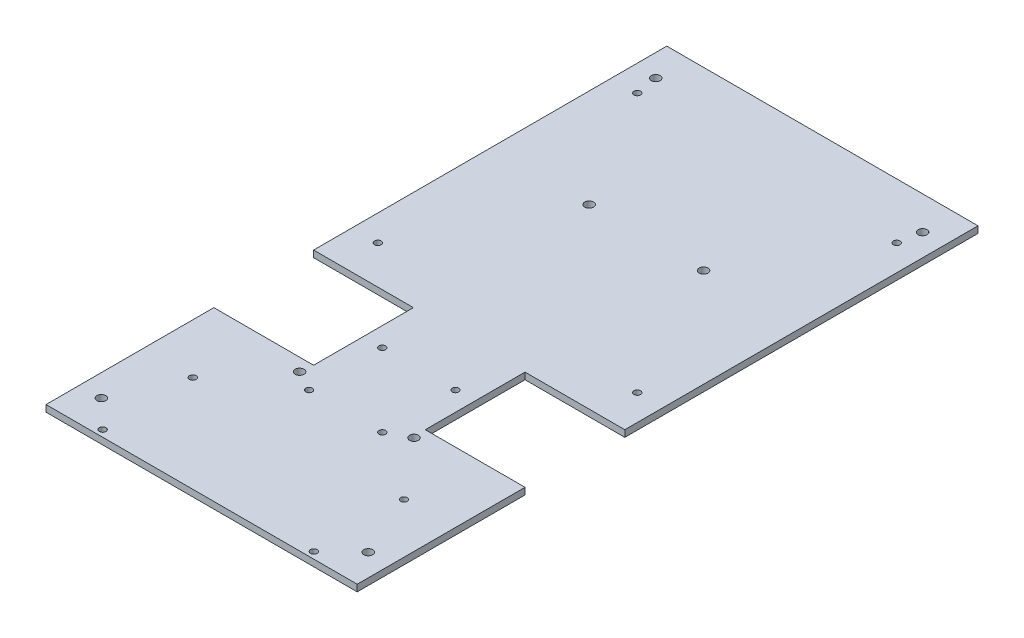
SolidWorks part; units mm, degrees
material "PMMA"
ref_plane "Front Plane" through (0, 0, 0) normal (0, 0, 1) x (1, 0, 0)
ref_plane "Top Plane" through (0, 0, 0) normal (0, 1, 0) x (1, 0, 0)
ref_plane "Right Plane" through (0, 0, 0) normal (1, 0, 0) x (0, 0, -1)
sketch "Schizzo1" plane through (0, 0, 0) normal (0, 1, 0) x (1, 0, 0)
  line L0 (-26.6704, 112.0472) -> (-26.6704, -167.9528) construction
  line L1 (-96.8504, 112.0472) -> (43.5096, 112.0472)
  line L2 (-96.8504, 112.0472) -> (-96.8504, -167.9528)
  line L3 (-96.8504, -167.9528) -> (43.5096, -167.9528)
  line L4 (43.5096, 112.0472) -> (43.5096, -167.9528)
  line L5 (-96.8504, -127.9528) -> (43.5096, -127.9528) construction
  line L6 (-96.8504, 12.0472) -> (43.5096, 12.0472) construction
  dimension "D1" = 280
  dimension "D2" = 140.36
  dimension "D3" = 40
  dimension "D4" = 100
extrude "Estrusione-Estrusione1" add sketch "Schizzo1" along normal blind 3
sketch "Schizzo2" plane through (0, 3, 0) normal (0, 1, 0) x (1, 0, 0)
  line L0 (-96.8504, 112.0472) -> (-96.8504, -167.9528) construction
  line L1 (-96.8504, -167.9528) -> (43.5096, -167.9528) construction
  line L2 (-26.6704, -167.9528) -> (-26.6704, 112.0472) construction
  line L3 (43.5096, 112.0472) -> (-96.8504, 112.0472) construction
  line L4 (-96.8504, -27.9528) -> (43.5096, -27.9528) construction
  line L5 (43.5096, -167.9528) -> (43.5096, 112.0472) construction
  circle A0 centre (-86.8504, -152.9528) radius 2
  circle A1 centre (33.5096, -152.9528) radius 2
  circle A2 centre (-86.8504, 97.0472) radius 2
  circle A3 centre (33.5096, 97.0472) radius 2
  point P16 (33.5096, 97.0472)
  dimension "D1" = 4
  dimension "D2" = 10
  dimension "D3" = 15
  dimension "D4" = 120.36
extrude "Taglio-Estrusione1" cut sketch "Schizzo2" along direction (0, 1, 0) on the side against the normal through all
sketch "Schizzo3" plane through (0, 0, 0) normal (0, 1, 0) x (1, 0, 0)
  line L0 (-96.8504, -92.2528) -> (43.5096, -92.2528) construction
  line L1 (-96.8504, 112.0472) -> (-96.8504, -167.9528) construction
  line L2 (43.5096, -167.9528) -> (43.5096, 112.0472) construction
  line L3 (-96.8504, -167.9528) -> (43.5096, -167.9528) construction
  line L4 (-26.6704, 112.0472) -> (-26.6704, -167.9528) construction
  line L5 (-96.8504, -92.2528) -> (-51.8504, -92.2528)
  line L6 (-96.8504, -92.2528) -> (-96.8504, -47.2528)
  line L7 (-96.8504, -47.2528) -> (-51.8504, -47.2528)
  line L8 (-51.8504, -92.2528) -> (-51.8504, -47.2528)
  line L9 (43.5096, 112.0472) -> (-96.8504, 112.0472) construction
  line L10 (43.5096, -92.2528) -> (43.5096, -47.2528)
  line L11 (43.5096, -92.2528) -> (-1.4904, -92.2528)
  line L12 (-1.4904, -92.2528) -> (-1.4904, -47.2528)
  line L13 (43.5096, -47.2528) -> (-1.4904, -47.2528)
  dimension "D1" = 75.7
  dimension "D2" = 45
  dimension "D3" = 45
extrude "Taglio-Estrusione2" cut sketch "Schizzo3" along direction (0, 1, 0) on the side of the normal through all
sketch "Schizzo4" plane through (0, 0, 0) normal (0, 1, 0) x (1, 0, 0)
  line L0 (-26.6704, 112.0472) -> (-26.6704, -167.9528) construction
  line L1 (-85.1704, 87.0472) -> (31.8296, 87.0472) construction
  line L2 (-85.1704, 87.0472) -> (-85.1704, -29.9528) construction
  line L3 (-85.1704, -29.9528) -> (31.8296, -29.9528) construction
  line L4 (31.8296, 87.0472) -> (31.8296, -29.9528) construction
  line L5 (43.5096, 112.0472) -> (-96.8504, 112.0472) construction
  line L6 (-96.8504, -167.9528) -> (43.5096, -167.9528) construction
  line L8 (-43.1804, -69.9528) -> (-10.1604, -69.9528) construction
  line L9 (-43.1804, -69.9528) -> (-43.1804, -102.9728) construction
  line L10 (-43.1804, -102.9728) -> (-10.1604, -102.9728) construction
  line L11 (-10.1604, -69.9528) -> (-10.1604, -102.9728) construction
  line L14 (-52.4704, 32.6472) -> (-0.8704, 32.6472) construction
  line L15 (-52.4704, 32.6472) -> (-52.4704, -97.9528) construction
  line L16 (-52.4704, -97.9528) -> (-0.8704, -97.9528) construction
  line L17 (-0.8704, 32.6472) -> (-0.8704, -97.9528) construction
  line L18 (-74.2954, -124.3128) -> (20.9546, -124.3128) construction
  line L19 (-74.2954, -124.3128) -> (-74.2954, -164.9528) construction
  line L20 (-74.2954, -164.9528) -> (20.9546, -164.9528) construction
  line L21 (20.9546, -124.3128) -> (20.9546, -164.9528) construction
  circle A0 centre (-85.1704, 87.0472) radius 1.5
  circle A1 centre (-85.1704, -29.9528) radius 1.5
  circle A2 centre (31.8296, -29.9528) radius 1.5
  circle A3 centre (31.8296, 87.0472) radius 1.5
  circle A4 centre (-43.1804, -69.9528) radius 1.5
  circle A5 centre (-10.1604, -69.9528) radius 1.5
  circle A6 centre (-10.1604, -102.9728) radius 1.5
  circle A7 centre (-43.1804, -102.9728) radius 1.5
  circle A8 centre (-52.4704, -97.9528) radius 2
  circle A9 centre (-0.8704, -97.9528) radius 2
  circle A10 centre (-0.8704, 32.6472) radius 2
  circle A11 centre (-52.4704, 32.6472) radius 2
  circle A12 centre (-74.2954, -124.3128) radius 1.5
  circle A13 centre (20.9546, -124.3128) radius 1.5
  circle A14 centre (20.9546, -164.9528) radius 1.5
  circle A15 centre (-74.2954, -164.9528) radius 1.5
  point P4 (-26.6704, 87.0472)
  point P19 (-26.6704, -69.9528)
  point P24 (-26.6704, 32.6472)
  point P37 (-26.6704, -124.3128)
  point P42 (-363.8822, -120.4176)
  dimension "D4" = 3
  dimension "D5" = 33.02
  dimension "D7" = 3
  dimension "D8" = 40
  dimension "D12" = 4
  dimension "D13" = 95.25
  dimension "D16" = 3
  dimension "D1" = 117
  dimension "D2" = 117
  dimension "D3" = 25
  dimension "D6" = 33.02
  dimension "D9" = 51.6
  dimension "D10" = 130.6
  dimension "D11" = 70
  dimension "D14" = 40.64
  dimension "D15" = 3
extrude "Taglio-Estrusione3" cut sketch "Schizzo4" along direction (0, 1, 0) on the side of the normal through all
equation "\"Thickness2\"= 2"
equation "\"Thickness3\"=3"
equation "\"D1@Estrusione-Estrusione1\"=\"Thickness3\""
